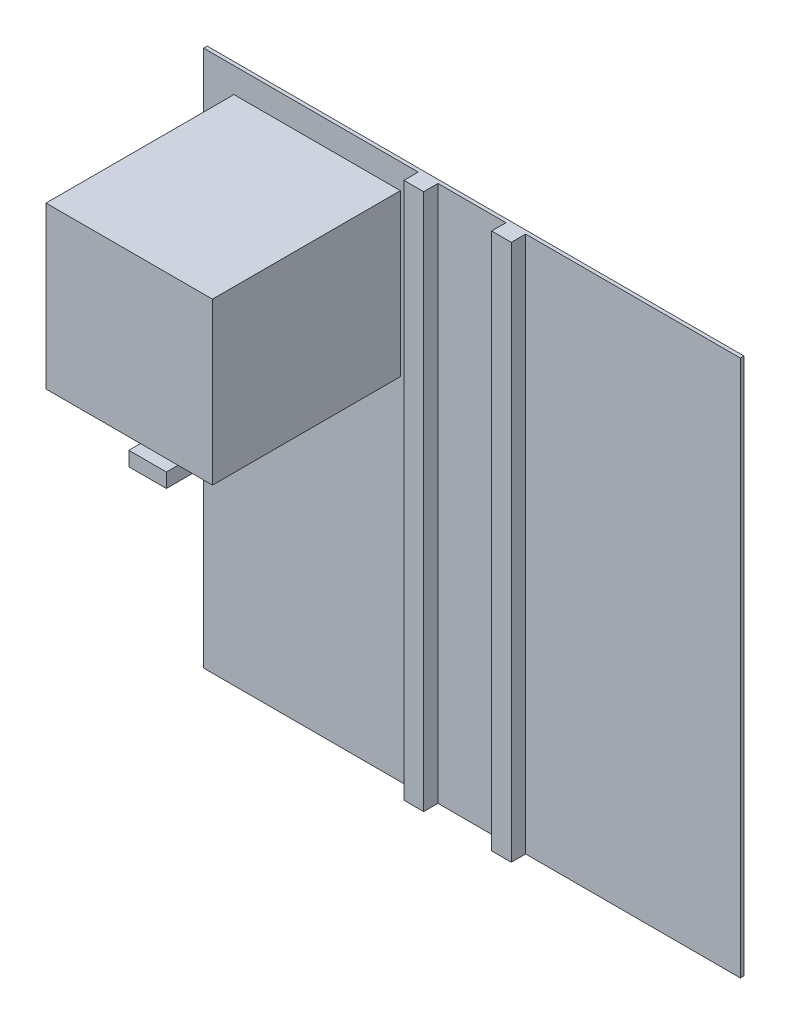
SolidWorks part; units mm, degrees
ref_plane "Front Plane" through (0, 0, 0) normal (0, 0, 1) x (1, 0, 0)
ref_plane "Top Plane" through (0, 0, 0) normal (0, 1, 0) x (1, 0, 0)
ref_plane "Right Plane" through (0, 0, 0) normal (1, 0, 0) x (0, 0, -1)
sketch "Sketch1" plane through (0, 0, 0) normal (0, 0, 1) x (1, 0, 0)
  line L1 (-1500, 1500) -> (0, 1500)
  line L2 (-1500, 1500) -> (-1500, 0)
  line L3 (-1500, 0) -> (0, 0)
  line L4 (0, 1500) -> (0, 0)
  dimension "D1" = 1500
extrude "Boss-Extrude1" add sketch "Sketch1" along normal blind 10
sketch "Sketch2" plane through (0, 0, 10) normal (0, 0, 1) x (1, 0, 0)
  line L0 (-750, 1500) -> (-750, 0) construction
  line L1 (0, 1500) -> (-1500, 1500) construction
  line L2 (-1500, 0) -> (0, 0) construction
  line L3 (-890, 1500) -> (-890, 0) construction
  line L4 (-610, 0) -> (-610, 1500) construction
  line L5 (-890, 1500) -> (-750, 1500) construction
  line L6 (-750, 1500) -> (-610, 1500) construction
  line L7 (-1500, 420) -> (0, 420) construction
  line L8 (-1415, 1430) -> (-950, 1430)
  line L9 (-1415, 1430) -> (-1415, 980)
  line L10 (-1415, 980) -> (-950, 980)
  line L11 (-950, 1430) -> (-950, 980)
  line L12 (-1500, 1500) -> (-1500, 0) construction
  line L13 (0, 0) -> (0, 1500) construction
  dimension "D1" = 280
  dimension "D2" = 60
  dimension "D3" = 450
  dimension "D4" = 465
  dimension "D5" = 560
  dimension "D6" = 70
extrude "Boss-Extrude2" add sketch "Sketch2" along normal blind 525
sketch "Sketch3" plane through (0, 980, 0) normal (0, -1, 0) x (1, 0, 0)
  line L0 (-1415, 272.5) -> (-950, 272.5) construction
  line L1 (-1151.1239, 567.5) -> (-1046.1239, 567.5)
  line L2 (-1151.1239, 567.5) -> (-1151.1239, 10)
  line L3 (-1151.1239, 10) -> (-1046.1239, 10)
  line L4 (-1046.1239, 567.5) -> (-1046.1239, 10)
  line L5 (-1500, 10) -> (0, 10) construction
  line L6 (-1098.6239, 567.5) -> (-1098.6239, 10) construction
  line L7 (-1415, 535) -> (-1415, 10) construction
  line L8 (-950, 535) -> (-950, 10) construction
  circle A0 centre (-1098.6239, 272.5) radius 85
  point P0 (-989.4848, 272.5)
  dimension "D3" = 170
  dimension "D1" = 295
  dimension "D2" = 105
extrude "Boss-Extrude3" add sketch "Sketch3" along normal blind 40 contours L2 L3 L4 L1
extrude "Boss-Extrude4" add sketch "Sketch3<3>" along normal blind 65 contours L4 A0 L2 region at (-1098.6239, 980, 272.5)
sketch "Sketch3<3>" plane through (0, 980, 0) normal (0, -1, 0) x (1, 0, 0) same geometry as "Sketch3"
sketch "Sketch4" plane through (0, 0, 10) normal (0, 0, 1) x (1, 0, 0)
  line L0 (0, 1500) -> (-1500, 1500) construction
  line L1 (-900, 1500) -> (-845, 1500)
  line L2 (-900, 1500) -> (-900, 0)
  line L3 (-900, 0) -> (-845, 0)
  line L4 (-845, 1500) -> (-845, 0)
  line L5 (-1500, 0) -> (0, 0) construction
  line L6 (-750, 0) -> (-750, 1500) construction
  line L7 (-600, 0) -> (-655, 0)
  line L8 (-655, 1500) -> (-655, 0)
  line L9 (-600, 1500) -> (-655, 1500)
  line L10 (-600, 1500) -> (-600, 0)
  dimension "D1" = 55
  dimension "D2" = 300
extrude "Boss-Extrude5" add sketch "Sketch4" along normal blind 40
